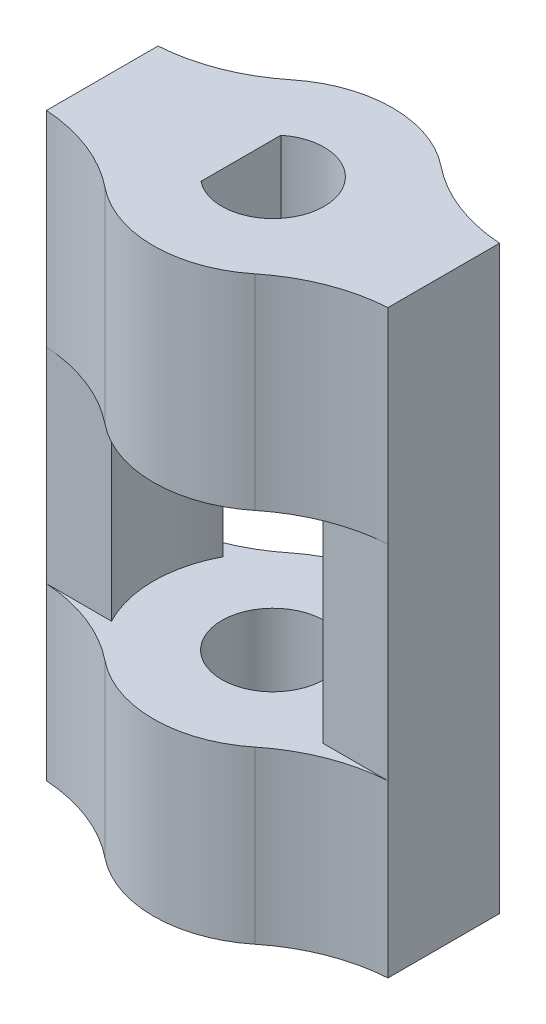
SolidWorks part; units mm, degrees
ref_plane "Front" through (0, 0, 0) normal (0, 0, 1) x (1, 0, 0)
ref_plane "Top" through (0, 0, 0) normal (0, 1, 0) x (1, 0, 0)
ref_plane "Right" through (0, 0, 0) normal (1, 0, 0) x (0, 0, -1)
sketch "Sketch1" plane through (0, 0, 0) normal (0, 1, 0) x (1, 0, 0)
  line L0 (-1.8776, 2.3398) -> (-1.8776, -2.3398)
  line L1 (-10, -3.2666) -> (10, -3.2666)
  line L2 (-10, -3.2666) -> (-10, 3.2666)
  line L3 (-10, 3.2666) -> (10, 3.2666)
  line L4 (10, -3.2666) -> (10, 3.2666)
  line L5 (-10, -3.2666) -> (10, 3.2666) construction
  line L6 (-10, 3.2666) -> (10, -3.2666) construction
  circle A0 centre (0, 0) radius 3
  circle A1 centre (0, 0) radius 7
  dimension "D1" = 6
  dimension "D2" = 4
  dimension "D3" = 20
extrude "Boss-Extrude1" add sketch "Sketch1" along normal blind 10 contours A1 L3 L2 L1 | L3 A1 | L1 A1 L3 A0 | L1 A1 | A1 L1 L4 L3 region at (-8.3597, 0, 0) region at (-6.8455, 0, 0) region at (0, 0, 4.8004) region at (8.3597, 0, 0) region at (0, 0, -4.8004)
extrude "Boss-Extrude2" add sketch "Sketch1<3>" along normal blind 12 from surface contours A1 L1 L4 L3 | A1 L3 L2 L1 region at (-8.3597, 0, 0) region at (8.3597, 0, 0) starting at face at (0, 10, 0)
sketch "Sketch1<3>" plane through (0, 0, 0) normal (0, 1, 0) x (1, 0, 0) same geometry as "Sketch1"
extrude "Boss-Extrude3" add sketch "Sketch1<5>" along normal blind 12 from surface contours A1 L3 L2 L1 | L0 A0 | L1 A1 | L3 A1 | L1 A1 L3 A0 | A1 L1 L4 L3 region at (-2.3346, 0, 0) region at (-8.3597, 0, 0) region at (-6.8455, 0, 0) region at (0, 0, 4.8004) region at (8.3597, 0, 0) region at (0, 0, -4.8004) starting at face at (-8.2978, 22, 0)
sketch "Sketch1<5>" plane through (0, 0, 0) normal (0, 1, 0) x (1, 0, 0) same geometry as "Sketch1"
fillet "Fillet1" radius 10 8 edges at (6.1911, 5, 3.2666) (6.1911, 28, 3.2666) (-6.1911, 5, 3.2666) (-6.1911, 28, 3.2666) (-6.1911, 28, -3.2666) (-6.1911, 5, -3.2666) (6.1911, 5, -3.2666) (6.1911, 28, -3.2666)
